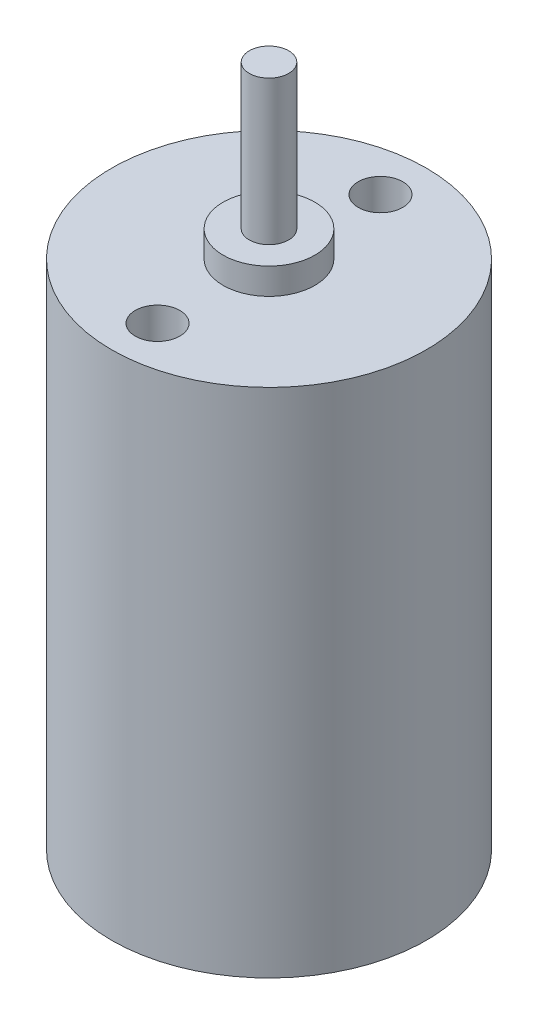
SolidWorks part; units mm, degrees
ref_plane "Front Plane" through (0, 0, 0) normal (0, 0, 1) x (1, 0, 0)
ref_plane "Top Plane" through (0, 0, 0) normal (0, 1, 0) x (1, 0, 0)
ref_plane "Right Plane" through (0, 0, 0) normal (1, 0, 0) x (0, 0, -1)
other "Center of Mass"
sketch "Sketch1" plane through (0, 0, 0) normal (0, 1, 0) x (1, 0, 0)
  circle A0 centre (0, 0) radius 12
extrude "Boss-Extrude1" add sketch "Sketch1" along normal blind 39
sketch "Sketch2" plane through (0, 39, 0) normal (0, 1, 0) x (1, 0, 0)
  circle A0 centre (0, 0) radius 3.5
extrude "Boss-Extrude2" add sketch "Sketch2" along normal blind 2
sketch "Sketch3" plane through (0, 41, 0) normal (0, 1, 0) x (1, 0, 0)
  circle A0 centre (0, 0) radius 1.5
extrude "Boss-Extrude3" add sketch "Sketch3" along normal blind 11
sketch "Sketch4" plane through (0, 39, 0) normal (0, 1, 0) x (1, 0, 0)
  circle A0 centre (0, 8.5) radius 1.7
  circle A1 centre (0, -8.5) radius 1.7
  circle A2 centre (0, 0) radius 12 construction
  dimension "D3" = 3.4
  dimension "D4" = 3.4
  dimension "D1" = 17
  dimension "D2" = 8.5
extrude "Cut-Extrude1" cut sketch "Sketch4" against normal blind 5
